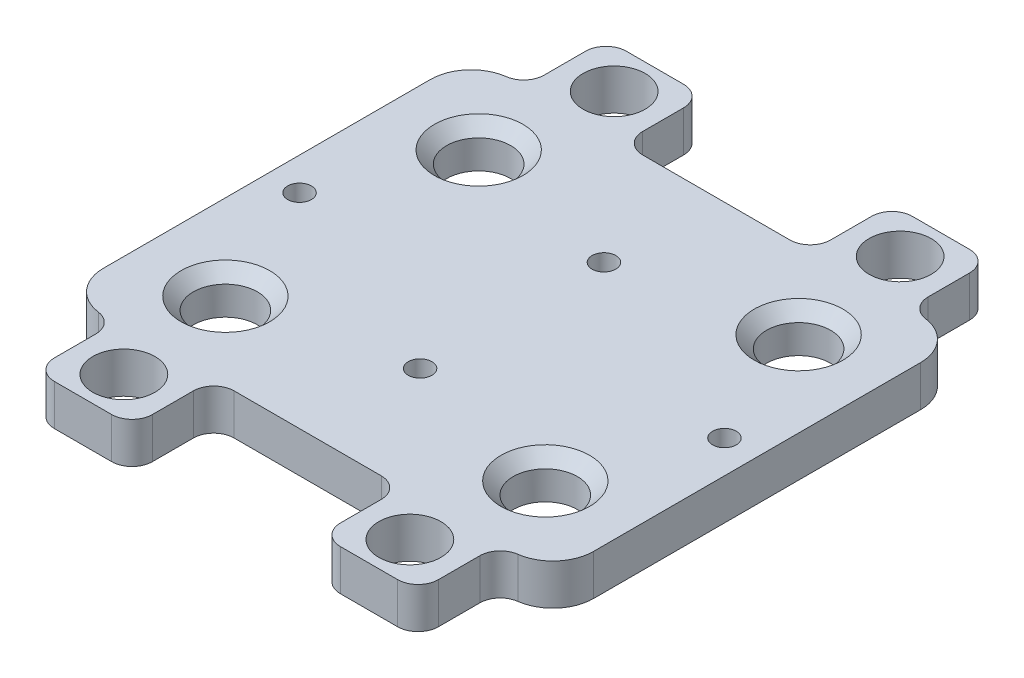
SolidWorks part; units mm, degrees
ref_plane "Front Plane" through (0, 0, 0) normal (0, 0, 1) x (1, 0, 0)
ref_plane "Top Plane" through (0, 0, 0) normal (0, 1, 0) x (1, 0, 0)
ref_plane "Right Plane" through (0, 0, 0) normal (1, 0, 0) x (0, 0, -1)
sketch "Sketch1" plane through (0, 0, 0) normal (1, 0, 0) x (0, 0, -1)
  line L1 (0, 0) -> (50, 0)
  line L2 (0, 0) -> (0, 5)
  line L3 (0, 5) -> (50, 5)
  line L4 (50, 0) -> (50, 5)
  dimension "D1" = 50
  dimension "D2" = 5
extrude "Boss-Extrude1" add sketch "Sketch1" along normal blind 60
sketch "Sketch2" plane through (0, 5, 0) normal (0, 1, 0) x (1, 0, 0)
  line L0 (60, 25) -> (0, 25) construction
  line L1 (60, 50) -> (60, 0) construction
  line L2 (0, 50) -> (0, 0) construction
  line L3 (41.5, 50) -> (41.5, 60)
  line L4 (30, 50) -> (30, 0) construction
  line L5 (60, 50) -> (0, 50) construction
  line L6 (60, 0) -> (0, 0) construction
  line L7 (6.5, 50) -> (18.5, 50)
  line L8 (6.5, 50) -> (6.5, 60)
  line L9 (6.5, 60) -> (18.5, 60)
  line L10 (18.5, 50) -> (18.5, 60)
  line L11 (53.5, 60) -> (41.5, 60)
  line L12 (53.5, 50) -> (53.5, 60)
  line L13 (53.5, 50) -> (41.5, 50)
  line L14 (53.5, 0) -> (41.5, 0)
  line L15 (53.5, 0) -> (53.5, -10)
  line L16 (53.5, -10) -> (41.5, -10)
  line L17 (18.5, 0) -> (18.5, -10)
  line L18 (6.5, -10) -> (18.5, -10)
  line L19 (6.5, 0) -> (6.5, -10)
  line L20 (6.5, 0) -> (18.5, 0)
  line L21 (41.5, 0) -> (41.5, -10)
  line L22 (12.5, 60) -> (12.5, 50) construction
  circle A0 centre (49.575, 40.5) radius 3.925
  circle A1 centre (10.425, 40.5) radius 3.925
  circle A2 centre (10.425, 9.5) radius 3.925
  circle A3 centre (49.575, 9.5) radius 3.925
  circle A5 centre (30, 36.25) radius 1.45
  circle A6 centre (30, 13.75) radius 1.45
  circle A7 centre (12.5, 55) radius 3.8
  circle A8 centre (47.5, 55) radius 3.8
  circle A9 centre (12.5, -5) radius 3.8
  circle A10 centre (47.5, -5) radius 3.8
  circle A11 centre (56, 25) radius 1.45
  circle A12 centre (4, 25) radius 1.45
  line M3 (0, 0) -> (60, 0)
  line M5 (60, 50) -> (0, 50)
  dimension "D2" = 7.85
  dimension "D5" = 2.9
  dimension "D6" = 2.9
  dimension "D12" = 7.6
  dimension "D9" = 2.9
  dimension "D1" = 15.5
  dimension "D7" = 11.25
  dimension "D8" = 11.25
  dimension "D4" = 4
  dimension "D10" = 10
  dimension "D11" = 12
  dimension "D3" = 5
  dimension "D13" = 6
  dimension "D14" = 12.5
extrude "Cut-Extrude1" cut sketch "Sketch2" against normal through all contours A0 | A11 | A6 | A3 | A2 | A12 | A1 | A5 region at (49.575, 5, -40.5) region at (10.425, 5, -9.5) region at (49.575, 5, -9.5) region at (30, 5, -13.75) region at (56, 5, -25) region at (4, 5, -25)
chamfer "Chamfer1" distance 1.5 angle 45 4 edges at (10.425, 5, -5.575) (49.575, 5, -5.575) (10.425, 5, -44.425) (49.575, 5, -36.575)
fillet "Fillet2" radius 5 4 edges at (0, 2.5, -50) (0, 2.5, 0) (60, 2.5, 0) (60, 2.5, -50)
extrude "Boss-Extrude2" add sketch "Sketch2<3>" against normal blind 5 contours L10 L9 L8 M5 | L12 L11 L3 M5 | L21 L16 L15 M3 | L19 L18 L17 M3 region at (41.6562, 5, -55) region at (12.5, 5, -50.1562) region at (53.3438, 5, 5) region at (18.3438, 5, 5)
sketch "Sketch2<3>" plane through (0, 5, 0) normal (0, 1, 0) x (1, 0, 0) same geometry as "Sketch2"
fillet "Fillet5" radius 2.5 8 edges at (41.5, 2.5, 10) (53.5, 2.5, 10) (6.5, 2.5, 10) (18.5, 2.5, 10) (53.5, 2.5, -60) (41.5, 2.5, -60) (6.5, 2.5, -60) (18.5, 2.5, -60)
fillet "Fillet6" radius 2.5 8 edges at (18.5, 2.5, 0) (53.5, 2.5, 0) (6.5, 2.5, 0) (41.5, 2.5, 0) (6.5, 2.5, -50) (41.5, 2.5, -50) (53.5, 2.5, -50) (18.5, 2.5, -50)
chamfer "Chamfer2" distance 1.5 angle 45 3 edges at (30, 0, -12.3) (56, 0, -23.55) (30, 0, -34.8)
chamfer "Chamfer3" distance 1.5 angle 45 1 edges at (4, 0, -23.55)
equation "\"width\"= 50"
equation "\"height\"= 5"
equation "\"D1@Sketch1\"=\"width\""
equation "\"D2@Sketch1\"=\"height\""
equation "\"D1@Boss-Extrude2\"=\"height\""
equation "\"height side thingies for axis\"= 10"
equation "\"width side thingies for axis\"= 12"
equation "\"height for circle\"= \"height side thingies for axis\" / 2"
equation "\"D10@Sketch2\"=\"height side thingies for axis\""
equation "\"D11@Sketch2\"=\"width side thingies for axis\""
equation "\"D3@Sketch2\"=\"height for circle\""
equation "\"width for circle\"= \"width side thingies for axis\" / 2"
equation "\"D13@Sketch2\"=\"width for circle\""
equation "\"width where side thing should be\"= \"width\" / 4"
equation "\"D14@Sketch2\"=\"width where side thing should be\""
